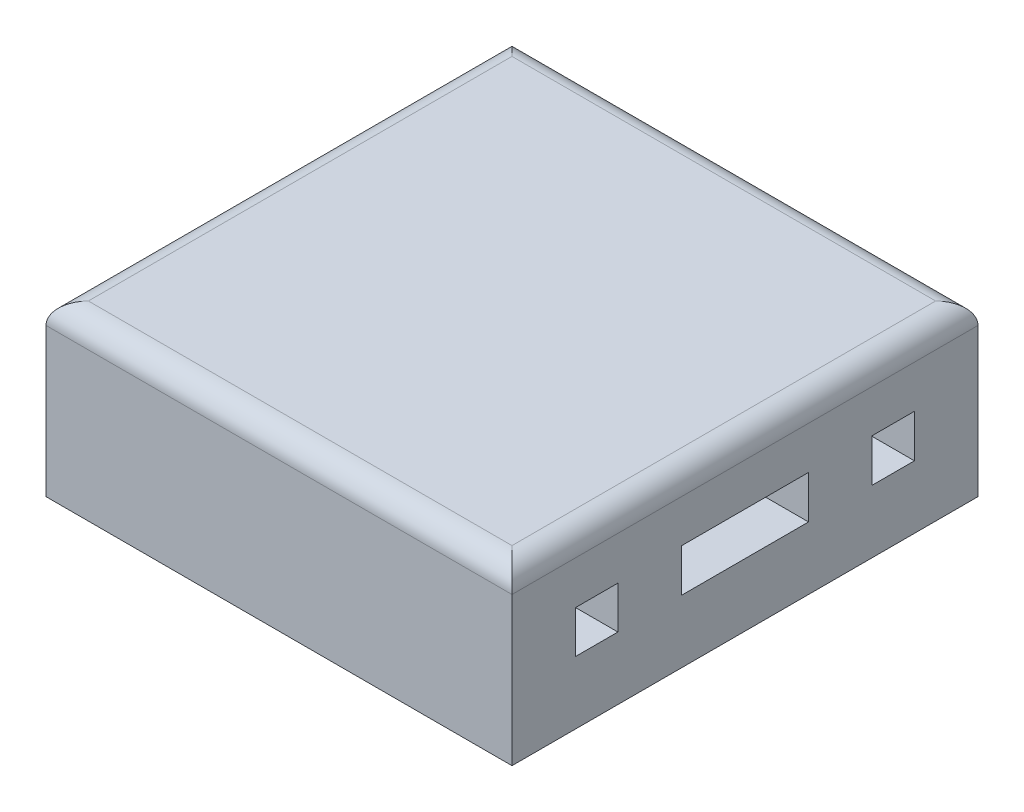
SolidWorks part; units mm, degrees
ref_plane "Front Plane" through (0, 0, 0) normal (0, 0, 1) x (1, 0, 0)
ref_plane "Top Plane" through (0, 0, 0) normal (0, 1, 0) x (1, 0, 0)
ref_plane "Right Plane" through (0, 0, 0) normal (1, 0, 0) x (0, 0, -1)
sketch "Sketch2" plane through (0, 0, 0) normal (0, 1, 0) x (1, 0, 0)
  line L0 (-5.5, -5.5) -> (5.5, -5.5)
  line L1 (0, 0) -> (0, 5.5)
  line L2 (-5.5, -5.5) -> (-5.5, 5.5)
  line L3 (-5.5, 5.5) -> (5.5, 5.5)
  line L4 (5.5, 5.5) -> (5.5, -5.5)
  line L5 (0, 0) -> (-5.5, 0)
  dimension "D1" = 11
  dimension "D2" = 11
  dimension "D3" = 5.5
  dimension "D4" = 5.5
extrude "Boss-Extrude1" add sketch "Sketch2" along normal blind 4 contours L0 L4 L3 L2
sketch "Sketch4" plane through (0, 0, 0) normal (1, 0, 0) x (0, 0, -1)
  line L0 (-4, 1.4828) -> (-4, 2.4828)
  line L1 (-1.5, 2.4957) -> (1.5, 2.4957)
  line L2 (5.5, 4) -> (5.5, 0) construction
  line L3 (-4, 1.4828) -> (-3, 1.4828)
  line L4 (-3, 1.4828) -> (-3, 2.4828)
  line L5 (-3, 2.4828) -> (-4, 2.4828)
  line L6 (-1.5, 1.4828) -> (-1.5, 2.4957)
  line L7 (1.5, 2.4957) -> (1.5, 1.4828)
  line L8 (1.5, 1.4828) -> (-1.5, 1.4828)
  line L9 (-5.5, 4) -> (-5.5, 0) construction
  line L10 (3, 1.4828) -> (3, 2.4957)
  line L11 (3, 2.4957) -> (4, 2.4957)
  line L12 (4, 2.4957) -> (4, 1.4828)
  line L13 (4, 1.4828) -> (3, 1.4828)
  dimension "D1" = 1.5
  dimension "D2" = 1.5
  dimension "D3" = 1.5
  dimension "D4" = 1
  dimension "D5" = 1
  dimension "D6" = 1
  dimension "D7" = 1.5
  dimension "D8" = 3
extrude "Cut-Extrude2" cut sketch "Sketch4" against normal through all both and the other way through all
sketch "Sketch5" plane through (0, 0, 0) normal (0, 1, 0) x (1, 0, 0)
  circle A0 centre (0, 0) radius 2.25
extrude "Cut-Extrude3" cut sketch "Sketch5" against normal through all and the other way blind 2.5
sketch "Sketch8" plane through (0, 0, 0) normal (0, 1, 0) x (1, 0, 0)
  line L0 (0, 0) -> (0, -4)
  line L1 (0, 0) -> (0, 4)
  line L2 (-5.5, -5.5) -> (5.5, -5.5) construction
  line L3 (-5.5, 5.5) -> (5.5, 5.5) construction
  circle A0 centre (0, 4) radius 1
  circle A1 centre (0, -4) radius 1
  dimension "D1" = 2
  dimension "D2" = 2
  dimension "D3" = 1.5
  dimension "D4" = 1.5
extrude "Cut-Extrude4" cut sketch "Sketch8" along normal blind 1 contours A1
extrude "Cut-Extrude5" cut sketch "Sketch8<3>" along normal blind 0.55 contours A0
sketch "Sketch8<3>" plane through (0, 0, 0) normal (0, 1, 0) x (1, 0, 0) same geometry as "Sketch8"
fillet "Fillet2" radius 0.5 4 edges at (0, 4, 5.5) (-5.5, 4, 0) (0, 4, -5.5) (5.5, 4, 0)
